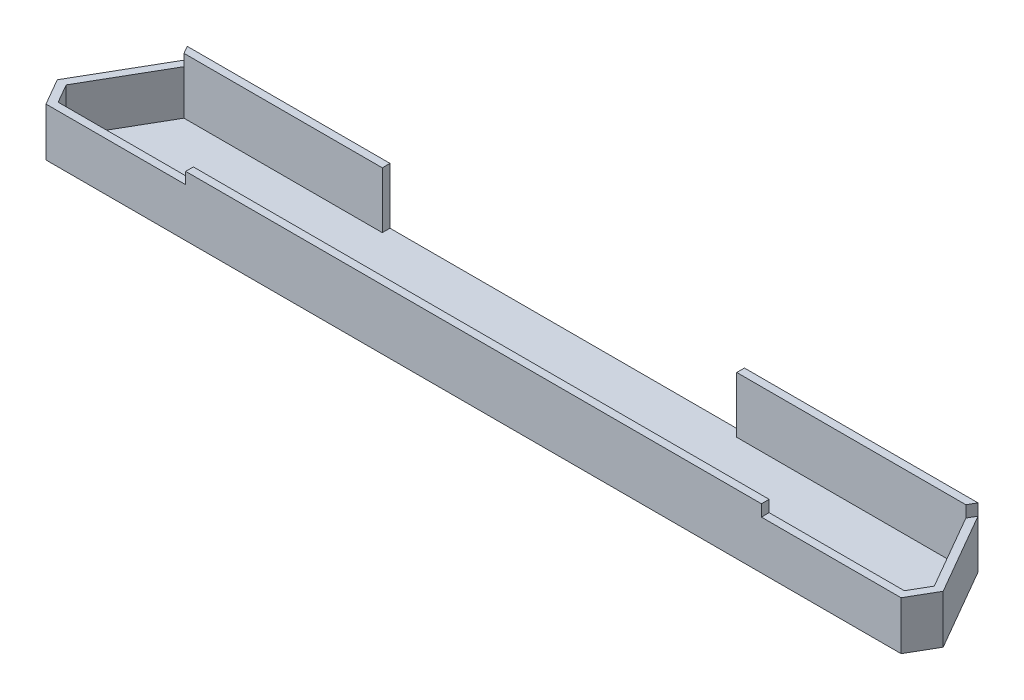
SolidWorks part; units mm, degrees
note: The reader was unsure of these and kept them because the rebuilt part matched: shared geometry of "Sketch1<3>", "Sketch1<4>", "Sketch1<5>".
ref_plane "Front Plane" through (0, 0, 0) normal (0, 0, 1) x (1, 0, 0)
ref_plane "Top Plane" through (0, 0, 0) normal (0, 1, 0) x (1, 0, 0)
ref_plane "Right Plane" through (0, 0, 0) normal (1, 0, 0) x (0, 0, -1)
sketch "Sketch1" plane through (0, 0, 0) normal (0, 1, 0) x (1, 0, 0)
  line L7 (-115, 0) -> (-111, -6.9282)
  line L9 (115, 0) -> (111, -6.9282)
  line L17 (-102.6494, 21.3918) -> (-101.4947, 19.3918)
  line L24 (102.6494, 21.3918) -> (101.4947, 19.3918)
  line L25 (-115, 0) -> (115, 0) construction
  line L26 (-115, 0) -> (-102.6494, 21.3918)
  line L27 (-113, -3.4641) -> (-107, 0) construction
  line L28 (0, -6.9282) -> (0, 21.3918) construction
  line L29 (113, -3.4641) -> (107, 0) construction
  line L30 (0, 21.3918) -> (-50.01, 21.3918) construction
  line L31 (-50.01, 21.3918) -> (-50.01, 19.3918)
  line L33 (-112.6906, 0) -> (-109.8453, -4.9282)
  line L36 (112.6906, 0) -> (109.8453, -4.9282)
  line L46 (-74.74, -4.9282) -> (74.74, -4.9282)
  line L49 (74.74, -6.9282) -> (-74.74, -6.9282)
  line L50 (-112.6906, 0) -> (-101.4947, 19.3918)
  line L51 (-102.6494, 21.3918) -> (-50.01, 21.3918)
  line L52 (-101.4947, 19.3918) -> (-50.01, 19.3918)
  line L53 (-50.01, 21.3918) -> (42.01, 21.3918) construction
  line L54 (42.01, 21.3918) -> (102.6494, 21.3918)
  line L55 (-109.8453, -4.9282) -> (-74.74, -4.9282)
  line L56 (109.8453, -4.9282) -> (74.74, -4.9282)
  line L57 (-111, -6.9282) -> (-74.74, -6.9282)
  line L59 (101.4947, 19.3918) -> (42.01, 19.3918)
  line L60 (102.6494, 21.3918) -> (115, 0)
  line L61 (42.01, 19.3918) -> (42.01, 21.3918)
  line L62 (101.4947, 19.3918) -> (112.6906, 0)
  line L63 (-50.01, 19.3918) -> (42.01, 19.3918)
  line L64 (-50.01, 21.3918) -> (42.01, 21.3918)
  line L68 (0, -6.9282) -> (-74.74, -6.9282) construction
  line L69 (-74.74, -6.9282) -> (-74.74, -4.9282)
  line L77 (111, -6.9282) -> (74.74, -6.9282)
  line L78 (74.74, -6.9282) -> (74.74, -4.9282)
  line L79 (0, -4.9282) -> (0, 19.3918) construction
  line L81 (0, 19.3918) -> (0, 21.3918) construction
  point P56 (0, 19.3918)
  point P60 (0, 21.3918)
  dimension "D1" = 8
  dimension "D3" = 8
  dimension "D4" = 230
  dimension "D5" = 92.02
  dimension "D6" = 42.01
  dimension "D7" = 74.74
extrude "Boss-Extrude1" add sketch "Sketch1" along normal blind 1
extrude "Boss-Extrude2" add sketch "Sketch1<3>" along normal blind 12.58
sketch "Sketch1<3>" plane through (0, 0, 0) normal (0, 1, 0) x (1, 0, 0) same geometry as "Sketch1"
extrude "Boss-Extrude3" add sketch "Sketch1<4>" along normal blind 15.58
sketch "Sketch1<4>" plane through (0, 0, 0) normal (0, 1, 0) x (1, 0, 0) same geometry as "Sketch1"
extrude "Boss-Extrude4" add sketch "Sketch1<5>" along normal blind 1 contours L64 L31 L63 L61
sketch "Sketch1<5>" plane through (0, 0, 0) normal (0, 1, 0) x (1, 0, 0) same geometry as "Sketch1"
